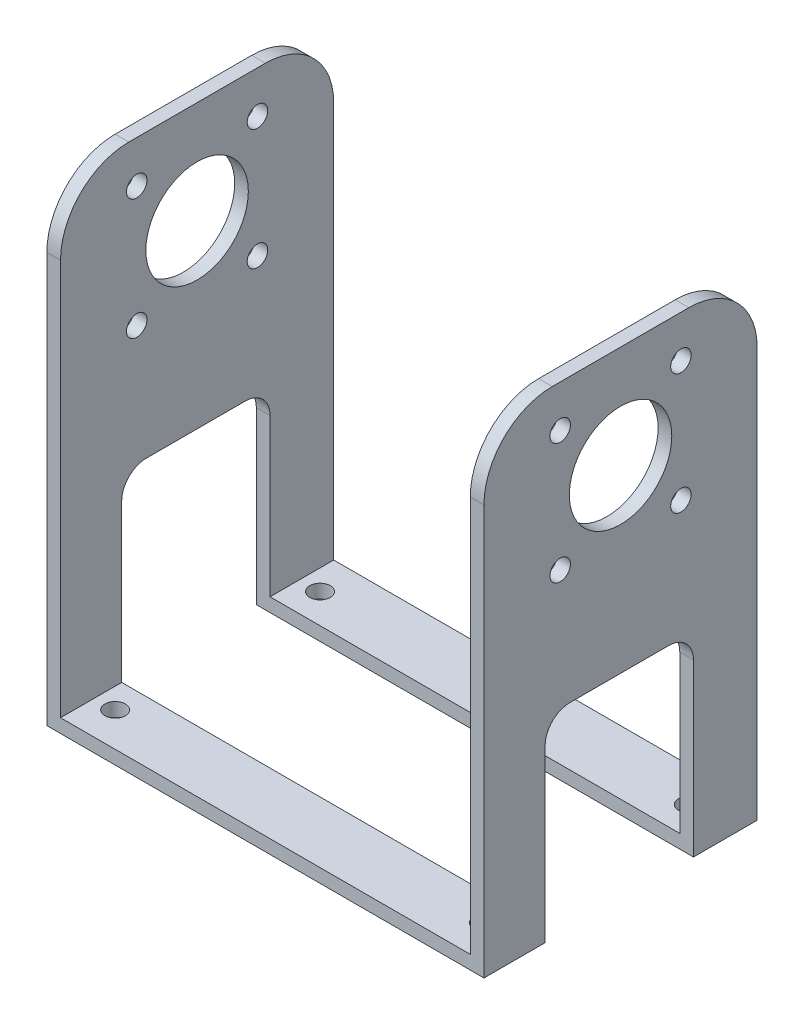
SolidWorks part; units mm, degrees
material "6061 Alloy"
ref_plane "Front Plane" through (0, 0, 0) normal (0, 0, 1) x (1, 0, 0)
ref_plane "Top Plane" through (0, 0, 0) normal (0, 1, 0) x (1, 0, 0)
ref_plane "Right Plane" through (0, 0, 0) normal (1, 0, 0) x (0, 0, -1)
sketch "Sketch1" plane through (0, 0, 0) normal (0, 0, 1) x (1, 0, 0)
  line L0 (-32, 0) -> (0, 0)
  line L1 (22, 0) -> (-22, 0) construction
  line L2 (0, 0) -> (0, 70)
  line L3 (0, -22) -> (0, 22) construction
  dimension "D1" = 70
  dimension "D2" = 32
extrude "Extrude-Thin1" add sketch "Sketch1" along normal blind 40 thin thin type one direction reverse wall 2
sketch "Sketch2" plane through (0, 0, 0) normal (1, 0, 0) x (0, 0, -1)
  line L0 (-31.0395, 0) -> (-31.0395, 25)
  line L1 (22, 0) -> (-22, 0) construction
  line L2 (-9.3277, 25) -> (-9.3277, 0)
  line L3 (-20, 70) -> (-20, 0) construction
  line L4 (-40, 70) -> (0, 70) construction
  line L5 (-31.0395, 0) -> (-9.3277, 0)
  line L6 (-27.4107, 28.6288) -> (-12.9564, 28.6288)
  arc A0 (-31.0395, 25) -> (-27.4107, 28.6288) centre (-27.4107, 25) cw
  circle A1 centre (-20, 55) radius 7.5
  arc A2 (-12.9564, 28.6288) -> (-9.3277, 25) centre (-12.9564, 25) cw
  dimension "D3" = 15
  dimension "D4" = 55
  dimension "D2" = 25
extrude "Cut-Extrude2" cut sketch "Sketch2" against normal blind 60 contours L3 A1 | A1 L3 | L2 L5 L0 A0 L6 A2 region at (0, 55, 23.1831) region at (0, 55, 16.8169)
fillet "Fillet1" radius 10 2 edges at (-1, 70, 0) (-1, 70, 40)
mirror "Mirror1" about plane through (-32, 0, 40) normal (-1, 0, 0) of bodies 103 104
sketch "Sketch3" plane through (0, 0, 0) normal (0, -1, 0) x (1, 0, 0)
  line L5 (-64, 40) -> (0, 40) construction
  line L6 (-59, 35) -> (-5, 35) construction
  line L7 (-59, 35) -> (-59, 5) construction
  line L8 (-59, 5) -> (-5, 5) construction
  line L9 (-5, 35) -> (-5, 5) construction
  line L10 (-64, 40) -> (-64, 31.0395) construction
  line L11 (0, -22) -> (0, 22) construction
  line L12 (35.2, 0) -> (-35.2, 0) construction
  circle A0 centre (-59, 35) radius 1.5
  circle A1 centre (-5, 35) radius 1.5
  circle A2 centre (-5, 5) radius 1.5
  circle A3 centre (-59, 5) radius 1.5
  dimension "D1" = 5
  dimension "D2" = 5
  dimension "D3" = 5
  dimension "D4" = 5
  dimension "D5" = 3
extrude "Cut-Extrude4" cut sketch "Sketch3" against normal blind 20
sketch "Sketch4" plane through (0, 0, 0) normal (1, 0, 0) x (0, 0, -1)
  line L0 (-11.1612, 63.8388) -> (-28.8388, 63.8388) construction
  line L1 (-28.8388, 63.8388) -> (-28.8388, 46.1612) construction
  circle A0 centre (-20, 55) radius 12.5 construction
  circle A1 centre (-28.8388, 63.8388) radius 1.5
  circle A2 centre (-11.1612, 63.8388) radius 1.5
  circle A3 centre (-11.1612, 46.1612) radius 1.5
  circle A4 centre (-28.8388, 46.1612) radius 1.5
  dimension "D1" = 3
  dimension "D2" = 25
extrude "Cut-Extrude5" cut sketch "Sketch4" against normal blind 140
